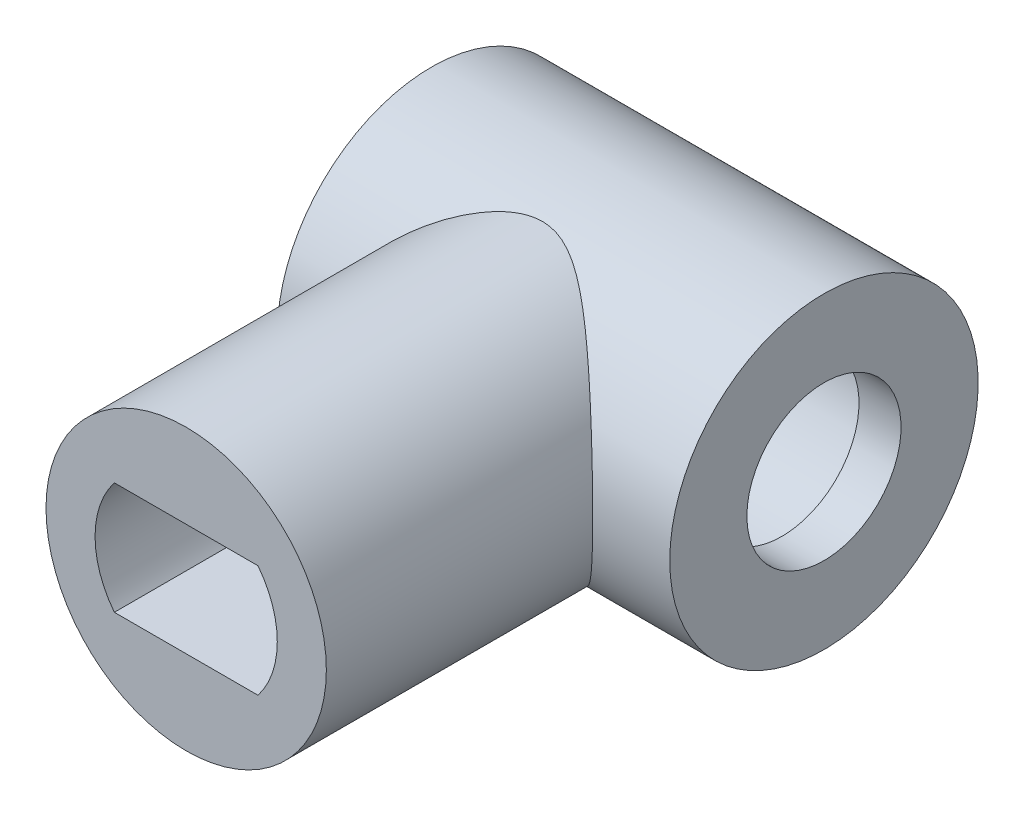
SolidWorks part; units mm, degrees
ref_plane "Front Plane" through (0, 0, 0) normal (0, 0, 1) x (1, 0, 0)
ref_plane "Top Plane" through (0, 0, 0) normal (0, 1, 0) x (1, 0, 0)
ref_plane "Right Plane" through (0, 0, 0) normal (1, 0, 0) x (0, 0, -1)
sketch "Sketch1" plane through (0, 0, 0) normal (0, 0, 1) x (1, 0, 0)
  line L0 (0, 3.2) -> (10, 3.2)
  line L4 (0, 0) -> (10, 0) construction
  line L5 (10, 3.2) -> (10, 2.2)
  line L6 (10, 2.2) -> (10, 0) construction
  line L7 (0, 3.2) -> (0, 0) construction
  dimension "D1" = 10
  dimension "D2" = 1
  dimension "D3" = 6.4
revolve "Revolve-Thin1" add sketch "Sketch1" angle 360 about L4 wall 1.2
ref_plane "Plane1" through (0, 0, 12) normal (0, 0, 1) x (1, 0, 0)
sketch "Sketch2" plane through (0, 0, 12) normal (0, 0, 1) x (1, 0, 0)
  line L0 (0, 0) -> (5, 0) construction
  line L1 (3, 1.5) -> (7, 1.5)
  line L2 (3, -1.5) -> (7, -1.5)
  arc A0 (3, 1.5) -> (3, -1.5) centre (5, 0) ccw
  arc A1 (7, 1.5) -> (3, 1.5) centre (5, 0) ccw construction
  arc A2 (7, -1.5) -> (7, 1.5) centre (5, 0) ccw
  arc A3 (3, -1.5) -> (7, -1.5) centre (5, 0) ccw construction
  circle A4 centre (5, 0) radius 4
  dimension "D1" = 5
  dimension "D4" = 1.5
  dimension "D2" = 3
  dimension "D3" = 5
extrude "Boss-Extrude1" add sketch "Sketch2" against normal up to surface (7.6 mm away) up to face at (11.2, 0, 4.4)
other "Move Face1" flip direction yes face at (2.75, -0.003, 8.1341) face at (5, 1.5, 8.0682) face at (7.25, 0.003, 8.1341) face at (5, -1.5, 8.0682) offset 0.1 parameters "D1"=0.1
